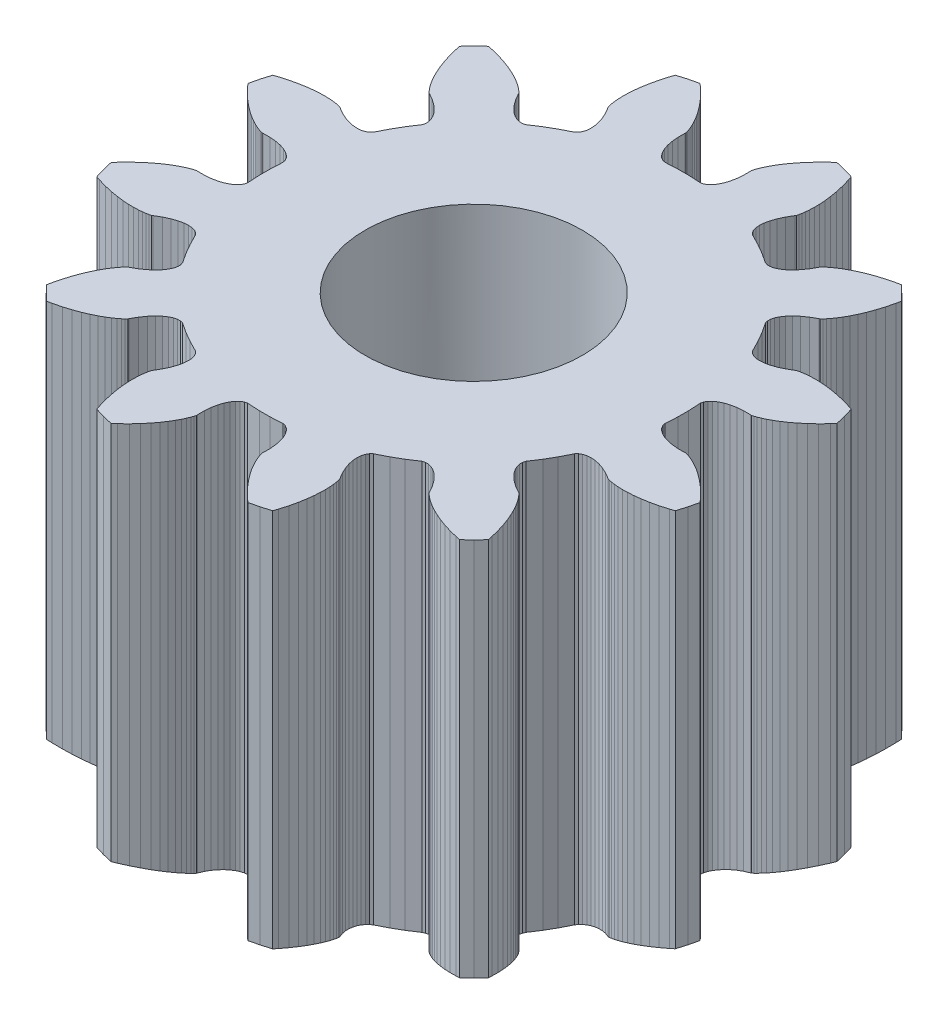
SolidWorks part; units mm, degrees
ref_plane "Front Plane" through (0, 0, 0) normal (0, 0, 1) x (1, 0, 0)
ref_plane "Top Plane" through (0, 0, 0) normal (0, 1, 0) x (1, 0, 0)
ref_plane "Right Plane" through (0, 0, 0) normal (1, 0, 0) x (0, 0, -1)
sketch "Sketch4" plane through (0, 0, 0) normal (0, 1, 0) x (1, 0, 0)
  line L0 (-8.5142, 2.5915) -> (-8.6005, 2.3068)
  line L1 (-8.6005, 2.3068) -> (-8.6681, 2.017)
  line L2 (-8.6681, 2.017) -> (-8.5825, 1.919)
  line L3 (-8.5825, 1.919) -> (-8.4064, 1.7373)
  line L4 (-8.4064, 1.7373) -> (-8.2355, 1.5786)
  line L5 (-8.2355, 1.5786) -> (-8.0717, 1.4418)
  line L6 (-8.0717, 1.4418) -> (-7.9169, 1.3256)
  line L7 (-7.9169, 1.3256) -> (-7.7726, 1.2287)
  line L8 (-7.7726, 1.2287) -> (-7.6405, 1.1497)
  line L9 (-7.6405, 1.1497) -> (-7.522, 1.087)
  line L10 (-7.522, 1.087) -> (-7.4183, 1.0389)
  line L11 (-7.4183, 1.0389) -> (-7.3306, 1.0037)
  line L12 (-7.3306, 1.0037) -> (-7.26, 0.9795)
  line L13 (-7.26, 0.9795) -> (-7.2073, 0.9645)
  line L14 (-7.2073, 0.9645) -> (-7.201, 0.9631)
  line L15 (-7.201, 0.9631) -> (-7.1713, 0.9658)
  line L16 (-7.1713, 0.9658) -> (-6.9676, 0.9668)
  line L17 (-6.9676, 0.9668) -> (-6.7838, 0.9501)
  line L18 (-6.7838, 0.9501) -> (-6.6212, 0.9179)
  line L19 (-6.6212, 0.9179) -> (-6.4809, 0.8724)
  line L20 (-6.4809, 0.8724) -> (-6.3638, 0.8157)
  line L21 (-6.3638, 0.8157) -> (-6.2706, 0.7503)
  line L22 (-6.2706, 0.7503) -> (-6.2018, 0.6785)
  line L23 (-6.2018, 0.6785) -> (-6.1577, 0.6025)
  line L24 (-6.1577, 0.6025) -> (-6.1387, 0.525)
  line L25 (-6.1387, 0.525) -> (-6.1577, 0.1615)
  line L26 (-6.1577, 0.1615) -> (-6.1577, -0.1615)
  line L27 (-6.1577, -0.1615) -> (-6.1387, -0.525)
  line L28 (-6.1387, -0.525) -> (-6.1577, -0.6025)
  line L29 (-6.1577, -0.6025) -> (-6.2018, -0.6785)
  line L30 (-6.2018, -0.6785) -> (-6.2706, -0.7503)
  line L31 (-6.2706, -0.7503) -> (-6.3638, -0.8157)
  line L32 (-6.3638, -0.8157) -> (-6.4809, -0.8724)
  line L33 (-6.4809, -0.8724) -> (-6.6212, -0.9179)
  line L34 (-6.6212, -0.9179) -> (-6.7838, -0.9501)
  line L35 (-6.7838, -0.9501) -> (-6.9676, -0.9668)
  line L36 (-6.9676, -0.9668) -> (-7.1713, -0.9658)
  line L37 (-7.1713, -0.9658) -> (-7.201, -0.9631)
  line L38 (-7.201, -0.9631) -> (-7.2073, -0.9645)
  line L39 (-7.2073, -0.9645) -> (-7.26, -0.9795)
  line L40 (-7.26, -0.9795) -> (-7.3306, -1.0037)
  line L41 (-7.3306, -1.0037) -> (-7.4183, -1.0389)
  line L42 (-7.4183, -1.0389) -> (-7.522, -1.087)
  line L43 (-7.522, -1.087) -> (-7.6405, -1.1497)
  line L44 (-7.6405, -1.1497) -> (-7.7726, -1.2287)
  line L45 (-7.7726, -1.2287) -> (-7.9169, -1.3256)
  line L46 (-7.9169, -1.3256) -> (-8.0717, -1.4418)
  line L47 (-8.0717, -1.4418) -> (-8.2355, -1.5786)
  line L48 (-8.2355, -1.5786) -> (-8.4064, -1.7373)
  line L49 (-8.4064, -1.7373) -> (-8.5825, -1.919)
  line L50 (-8.5825, -1.919) -> (-8.6681, -2.017)
  line L51 (-8.6681, -2.017) -> (-8.6005, -2.3068)
  line L52 (-8.6005, -2.3068) -> (-8.5142, -2.5915)
  line L53 (-8.5142, -2.5915) -> (-8.391, -2.6336)
  line L54 (-8.391, -2.6336) -> (-8.1477, -2.7029)
  line L55 (-8.1477, -2.7029) -> (-7.9203, -2.7549)
  line L56 (-7.9203, -2.7549) -> (-7.7101, -2.7915)
  line L57 (-7.7101, -2.7915) -> (-7.5179, -2.8147)
  line L58 (-7.5179, -2.8147) -> (-7.3445, -2.8264)
  line L59 (-7.3445, -2.8264) -> (-7.1906, -2.8288)
  line L60 (-7.1906, -2.8288) -> (-7.0566, -2.8239)
  line L61 (-7.0566, -2.8239) -> (-6.9428, -2.8137)
  line L62 (-6.9428, -2.8137) -> (-6.8492, -2.8003)
  line L63 (-6.8492, -2.8003) -> (-6.776, -2.7859)
  line L64 (-6.776, -2.7859) -> (-6.7228, -2.7726)
  line L65 (-6.7228, -2.7726) -> (-6.7167, -2.7707)
  line L66 (-6.7167, -2.7707) -> (-6.6923, -2.7535)
  line L67 (-6.6923, -2.7535) -> (-6.5163, -2.6507)
  line L68 (-6.5163, -2.6507) -> (-6.3489, -2.5733)
  line L69 (-6.3489, -2.5733) -> (-6.192, -2.5199)
  line L70 (-6.192, -2.5199) -> (-6.0477, -2.4892)
  line L71 (-6.0477, -2.4892) -> (-5.918, -2.4797)
  line L72 (-5.918, -2.4797) -> (-5.8045, -2.4897)
  line L73 (-5.8045, -2.4897) -> (-5.709, -2.5176)
  line L74 (-5.709, -2.5176) -> (-5.6329, -2.5613)
  line L75 (-5.6329, -2.5613) -> (-5.5776, -2.6189)
  line L76 (-5.5776, -2.6189) -> (-5.4124, -2.9433)
  line L77 (-5.4124, -2.9433) -> (-5.2509, -3.2229)
  line L78 (-5.2509, -3.2229) -> (-5.0526, -3.5282)
  line L79 (-5.0526, -3.5282) -> (-5.0304, -3.6049)
  line L80 (-5.0304, -3.6049) -> (-5.0305, -3.6927)
  line L81 (-5.0305, -3.6927) -> (-5.0542, -3.7893)
  line L82 (-5.0542, -3.7893) -> (-5.1022, -3.8926)
  line L83 (-5.1022, -3.8926) -> (-5.1753, -4.0002)
  line L84 (-5.1753, -4.0002) -> (-5.2741, -4.1098)
  line L85 (-5.2741, -4.1098) -> (-5.3987, -4.219)
  line L86 (-5.3987, -4.219) -> (-5.5496, -4.3253)
  line L87 (-5.5496, -4.3253) -> (-5.7265, -4.4263)
  line L88 (-5.7265, -4.4263) -> (-5.7536, -4.4388)
  line L89 (-5.7536, -4.4388) -> (-5.7583, -4.4432)
  line L90 (-5.7583, -4.4432) -> (-5.7965, -4.4825)
  line L91 (-5.7965, -4.4825) -> (-5.8455, -4.5388)
  line L92 (-5.8455, -4.5388) -> (-5.9039, -4.6131)
  line L93 (-5.9039, -4.6131) -> (-5.9696, -4.7066)
  line L94 (-5.9696, -4.7066) -> (-6.0409, -4.8202)
  line L95 (-6.0409, -4.8202) -> (-6.1158, -4.9546)
  line L96 (-6.1158, -4.9546) -> (-6.1923, -5.1107)
  line L97 (-6.1923, -5.1107) -> (-6.2683, -5.2887)
  line L98 (-6.2683, -5.2887) -> (-6.3417, -5.4891)
  line L99 (-6.3417, -5.4891) -> (-6.4104, -5.712)
  line L100 (-6.4104, -5.712) -> (-6.4721, -5.9574)
  line L101 (-6.4721, -5.9574) -> (-6.4972, -6.085)
  line L102 (-6.4972, -6.085) -> (-6.2938, -6.3022)
  line L103 (-6.2938, -6.3022) -> (-6.0766, -6.5056)
  line L104 (-6.0766, -6.5056) -> (-5.9489, -6.4805)
  line L105 (-5.9489, -6.4805) -> (-5.7035, -6.4188)
  line L106 (-5.7035, -6.4188) -> (-5.4806, -6.3502)
  line L107 (-5.4806, -6.3502) -> (-5.2802, -6.2768)
  line L108 (-5.2802, -6.2768) -> (-5.1022, -6.2008)
  line L109 (-5.1022, -6.2008) -> (-4.9462, -6.1243)
  line L110 (-4.9462, -6.1243) -> (-4.8117, -6.0494)
  line L111 (-4.8117, -6.0494) -> (-4.6981, -5.9781)
  line L112 (-4.6981, -5.9781) -> (-4.6046, -5.9123)
  line L113 (-4.6046, -5.9123) -> (-4.5303, -5.854)
  line L114 (-4.5303, -5.854) -> (-4.4741, -5.8049)
  line L115 (-4.4741, -5.8049) -> (-4.4347, -5.7667)
  line L116 (-4.4347, -5.7667) -> (-4.4304, -5.7621)
  line L117 (-4.4304, -5.7621) -> (-4.4178, -5.7349)
  line L118 (-4.4178, -5.7349) -> (-4.3168, -5.558)
  line L119 (-4.3168, -5.558) -> (-4.2105, -5.4072)
  line L120 (-4.2105, -5.4072) -> (-4.1013, -5.2825)
  line L121 (-4.1013, -5.2825) -> (-3.9917, -5.1838)
  line L122 (-3.9917, -5.1838) -> (-3.8841, -5.1107)
  line L123 (-3.8841, -5.1107) -> (-3.7809, -5.0626)
  line L124 (-3.7809, -5.0626) -> (-3.6842, -5.039)
  line L125 (-3.6842, -5.039) -> (-3.5965, -5.0388)
  line L126 (-3.5965, -5.0388) -> (-3.5198, -5.0611)
  line L127 (-3.5198, -5.0611) -> (-3.2145, -5.2594)
  line L128 (-3.2145, -5.2594) -> (-2.9348, -5.4208)
  line L129 (-2.9348, -5.4208) -> (-2.6105, -5.5861)
  line L130 (-2.6105, -5.5861) -> (-2.5528, -5.6414)
  line L131 (-2.5528, -5.6414) -> (-2.5091, -5.7174)
  line L132 (-2.5091, -5.7174) -> (-2.4813, -5.813)
  line L133 (-2.4813, -5.813) -> (-2.4712, -5.9264)
  line L134 (-2.4712, -5.9264) -> (-2.4807, -6.0562)
  line L135 (-2.4807, -6.0562) -> (-2.5114, -6.2004)
  line L136 (-2.5114, -6.2004) -> (-2.5648, -6.3573)
  line L137 (-2.5648, -6.3573) -> (-2.6423, -6.5248)
  line L138 (-2.6423, -6.5248) -> (-2.745, -6.7007)
  line L139 (-2.745, -6.7007) -> (-2.7622, -6.7252)
  line L140 (-2.7622, -6.7252) -> (-2.7641, -6.7313)
  line L141 (-2.7641, -6.7313) -> (-2.7775, -6.7844)
  line L142 (-2.7775, -6.7844) -> (-2.7919, -6.8577)
  line L143 (-2.7919, -6.8577) -> (-2.8052, -6.9512)
  line L144 (-2.8052, -6.9512) -> (-2.8154, -7.065)
  line L145 (-2.8154, -7.065) -> (-2.8204, -7.1991)
  line L146 (-2.8204, -7.1991) -> (-2.818, -7.353)
  line L147 (-2.818, -7.353) -> (-2.8062, -7.5263)
  line L148 (-2.8062, -7.5263) -> (-2.783, -7.7185)
  line L149 (-2.783, -7.7185) -> (-2.7464, -7.9288)
  line L150 (-2.7464, -7.9288) -> (-2.6944, -8.1561)
  line L151 (-2.6944, -8.1561) -> (-2.6252, -8.3995)
  line L152 (-2.6252, -8.3995) -> (-2.5831, -8.5226)
  line L153 (-2.5831, -8.5226) -> (-2.2983, -8.609)
  line L154 (-2.2983, -8.609) -> (-2.0085, -8.6766)
  line L155 (-2.0085, -8.6766) -> (-1.9105, -8.591)
  line L156 (-1.9105, -8.591) -> (-1.7288, -8.4148)
  line L157 (-1.7288, -8.4148) -> (-1.5701, -8.2439)
  line L158 (-1.5701, -8.2439) -> (-1.4333, -8.0802)
  line L159 (-1.4333, -8.0802) -> (-1.3171, -7.9253)
  line L160 (-1.3171, -7.9253) -> (-1.2203, -7.7811)
  line L161 (-1.2203, -7.7811) -> (-1.1413, -7.649)
  line L162 (-1.1413, -7.649) -> (-1.0785, -7.5304)
  line L163 (-1.0785, -7.5304) -> (-1.0304, -7.4268)
  line L164 (-1.0304, -7.4268) -> (-0.9952, -7.3391)
  line L165 (-0.9952, -7.3391) -> (-0.9711, -7.2685)
  line L166 (-0.9711, -7.2685) -> (-0.9561, -7.2157)
  line L167 (-0.9561, -7.2157) -> (-0.9547, -7.2095)
  line L168 (-0.9547, -7.2095) -> (-0.9573, -7.1797)
  line L169 (-0.9573, -7.1797) -> (-0.9583, -6.976)
  line L170 (-0.9583, -6.976) -> (-0.9417, -6.7922)
  line L171 (-0.9417, -6.7922) -> (-0.9095, -6.6297)
  line L172 (-0.9095, -6.6297) -> (-0.8639, -6.4894)
  line L173 (-0.8639, -6.4894) -> (-0.8073, -6.3723)
  line L174 (-0.8073, -6.3723) -> (-0.7419, -6.279)
  line L175 (-0.7419, -6.279) -> (-0.67, -6.2102)
  line L176 (-0.67, -6.2102) -> (-0.5941, -6.1662)
  line L177 (-0.5941, -6.1662) -> (-0.5165, -6.1471)
  line L178 (-0.5165, -6.1471) -> (-0.153, -6.1662)
  line L179 (-0.153, -6.1662) -> (0.1699, -6.1662)
  line L180 (0.1699, -6.1662) -> (0.5334, -6.1471)
  line L181 (0.5334, -6.1471) -> (0.611, -6.1662)
  line L182 (0.611, -6.1662) -> (0.6869, -6.2102)
  line L183 (0.6869, -6.2102) -> (0.7588, -6.279)
  line L184 (0.7588, -6.279) -> (0.8242, -6.3723)
  line L185 (0.8242, -6.3723) -> (0.8808, -6.4894)
  line L186 (0.8808, -6.4894) -> (0.9264, -6.6297)
  line L187 (0.9264, -6.6297) -> (0.9586, -6.7922)
  line L188 (0.9586, -6.7922) -> (0.9752, -6.976)
  line L189 (0.9752, -6.976) -> (0.9742, -7.1797)
  line L190 (0.9742, -7.1797) -> (0.9716, -7.2095)
  line L191 (0.9716, -7.2095) -> (0.973, -7.2157)
  line L192 (0.973, -7.2157) -> (0.988, -7.2685)
  line L193 (0.988, -7.2685) -> (1.0121, -7.3391)
  line L194 (1.0121, -7.3391) -> (1.0474, -7.4268)
  line L195 (1.0474, -7.4268) -> (1.0954, -7.5304)
  line L196 (1.0954, -7.5304) -> (1.1582, -7.649)
  line L197 (1.1582, -7.649) -> (1.2372, -7.7811)
  line L198 (1.2372, -7.7811) -> (1.334, -7.9253)
  line L199 (1.334, -7.9253) -> (1.4502, -8.0802)
  line L200 (1.4502, -8.0802) -> (1.587, -8.2439)
  line L201 (1.587, -8.2439) -> (1.7457, -8.4148)
  line L202 (1.7457, -8.4148) -> (1.9274, -8.591)
  line L203 (1.9274, -8.591) -> (2.0254, -8.6766)
  line L204 (2.0254, -8.6766) -> (2.3152, -8.609)
  line L205 (2.3152, -8.609) -> (2.6, -8.5226)
  line L206 (2.6, -8.5226) -> (2.6421, -8.3995)
  line L207 (2.6421, -8.3995) -> (2.7113, -8.1561)
  line L208 (2.7113, -8.1561) -> (2.7633, -7.9288)
  line L209 (2.7633, -7.9288) -> (2.7999, -7.7185)
  line L210 (2.7999, -7.7185) -> (2.8231, -7.5263)
  line L211 (2.8231, -7.5263) -> (2.8349, -7.353)
  line L212 (2.8349, -7.353) -> (2.8373, -7.1991)
  line L213 (2.8373, -7.1991) -> (2.8323, -7.065)
  line L214 (2.8323, -7.065) -> (2.8221, -6.9512)
  line L215 (2.8221, -6.9512) -> (2.8088, -6.8577)
  line L216 (2.8088, -6.8577) -> (2.7944, -6.7844)
  line L217 (2.7944, -6.7844) -> (2.781, -6.7313)
  line L218 (2.781, -6.7313) -> (2.7791, -6.7252)
  line L219 (2.7791, -6.7252) -> (2.7619, -6.7007)
  line L220 (2.7619, -6.7007) -> (2.6592, -6.5248)
  line L221 (2.6592, -6.5248) -> (2.5817, -6.3573)
  line L222 (2.5817, -6.3573) -> (2.5283, -6.2004)
  line L223 (2.5283, -6.2004) -> (2.4976, -6.0562)
  line L224 (2.4976, -6.0562) -> (2.4881, -5.9264)
  line L225 (2.4881, -5.9264) -> (2.4982, -5.813)
  line L226 (2.4982, -5.813) -> (2.526, -5.7174)
  line L227 (2.526, -5.7174) -> (2.5697, -5.6414)
  line L228 (2.5697, -5.6414) -> (2.6274, -5.5861)
  line L229 (2.6274, -5.5861) -> (2.9517, -5.4208)
  line L230 (2.9517, -5.4208) -> (3.2314, -5.2594)
  line L231 (3.2314, -5.2594) -> (3.5367, -5.0611)
  line L232 (3.5367, -5.0611) -> (3.6134, -5.0388)
  line L233 (3.6134, -5.0388) -> (3.7011, -5.039)
  line L234 (3.7011, -5.039) -> (3.7978, -5.0626)
  line L235 (3.7978, -5.0626) -> (3.901, -5.1107)
  line L236 (3.901, -5.1107) -> (4.0087, -5.1838)
  line L237 (4.0087, -5.1838) -> (4.1182, -5.2825)
  line L238 (4.1182, -5.2825) -> (4.2274, -5.4072)
  line L239 (4.2274, -5.4072) -> (4.3337, -5.558)
  line L240 (4.3337, -5.558) -> (4.4347, -5.7349)
  line L241 (4.4347, -5.7349) -> (4.4473, -5.7621)
  line L242 (4.4473, -5.7621) -> (4.4516, -5.7667)
  line L243 (4.4516, -5.7667) -> (4.491, -5.8049)
  line L244 (4.491, -5.8049) -> (4.5472, -5.854)
  line L245 (4.5472, -5.854) -> (4.6215, -5.9123)
  line L246 (4.6215, -5.9123) -> (4.715, -5.9781)
  line L247 (4.715, -5.9781) -> (4.8286, -6.0494)
  line L248 (4.8286, -6.0494) -> (4.9631, -6.1243)
  line L249 (4.9631, -6.1243) -> (5.1191, -6.2008)
  line L250 (5.1191, -6.2008) -> (5.2971, -6.2768)
  line L251 (5.2971, -6.2768) -> (5.4975, -6.3502)
  line L252 (5.4975, -6.3502) -> (5.7204, -6.4188)
  line L253 (5.7204, -6.4188) -> (5.9658, -6.4805)
  line L254 (5.9658, -6.4805) -> (6.0935, -6.5056)
  line L255 (6.0935, -6.5056) -> (6.3107, -6.3022)
  line L256 (6.3107, -6.3022) -> (6.5141, -6.085)
  line L257 (6.5141, -6.085) -> (6.489, -5.9574)
  line L258 (6.489, -5.9574) -> (6.4273, -5.712)
  line L259 (6.4273, -5.712) -> (6.3586, -5.4891)
  line L260 (6.3586, -5.4891) -> (6.2852, -5.2887)
  line L261 (6.2852, -5.2887) -> (6.2092, -5.1107)
  line L262 (6.2092, -5.1107) -> (6.1327, -4.9546)
  line L263 (6.1327, -4.9546) -> (6.0578, -4.8202)
  line L264 (6.0578, -4.8202) -> (5.9865, -4.7066)
  line L265 (5.9865, -4.7066) -> (5.9208, -4.6131)
  line L266 (5.9208, -4.6131) -> (5.8624, -4.5388)
  line L267 (5.8624, -4.5388) -> (5.8134, -4.4825)
  line L268 (5.8134, -4.4825) -> (5.7752, -4.4432)
  line L269 (5.7752, -4.4432) -> (5.7705, -4.4388)
  line L270 (5.7705, -4.4388) -> (5.7434, -4.4263)
  line L271 (5.7434, -4.4263) -> (5.5665, -4.3253)
  line L272 (5.5665, -4.3253) -> (5.4156, -4.219)
  line L273 (5.4156, -4.219) -> (5.291, -4.1098)
  line L274 (5.291, -4.1098) -> (5.1922, -4.0002)
  line L275 (5.1922, -4.0002) -> (5.1191, -3.8926)
  line L276 (5.1191, -3.8926) -> (5.0711, -3.7893)
  line L277 (5.0711, -3.7893) -> (5.0474, -3.6927)
  line L278 (5.0474, -3.6927) -> (5.0473, -3.6049)
  line L279 (5.0473, -3.6049) -> (5.0695, -3.5282)
  line L280 (5.0695, -3.5282) -> (5.2678, -3.2229)
  line L281 (5.2678, -3.2229) -> (5.4293, -2.9433)
  line L282 (5.4293, -2.9433) -> (5.5945, -2.6189)
  line L283 (5.5945, -2.6189) -> (5.6498, -2.5613)
  line L284 (5.6498, -2.5613) -> (5.7259, -2.5176)
  line L285 (5.7259, -2.5176) -> (5.8214, -2.4897)
  line L286 (5.8214, -2.4897) -> (5.9349, -2.4797)
  line L287 (5.9349, -2.4797) -> (6.0646, -2.4892)
  line L288 (6.0646, -2.4892) -> (6.2089, -2.5199)
  line L289 (6.2089, -2.5199) -> (6.3658, -2.5733)
  line L290 (6.3658, -2.5733) -> (6.5332, -2.6507)
  line L291 (6.5332, -2.6507) -> (6.7092, -2.7535)
  line L292 (6.7092, -2.7535) -> (6.7336, -2.7707)
  line L293 (6.7336, -2.7707) -> (6.7397, -2.7726)
  line L294 (6.7397, -2.7726) -> (6.7929, -2.7859)
  line L295 (6.7929, -2.7859) -> (6.8661, -2.8003)
  line L296 (6.8661, -2.8003) -> (6.9597, -2.8137)
  line L297 (6.9597, -2.8137) -> (7.0735, -2.8239)
  line L298 (7.0735, -2.8239) -> (7.2075, -2.8288)
  line L299 (7.2075, -2.8288) -> (7.3614, -2.8264)
  line L300 (7.3614, -2.8264) -> (7.5348, -2.8147)
  line L301 (7.5348, -2.8147) -> (7.727, -2.7915)
  line L302 (7.727, -2.7915) -> (7.9372, -2.7549)
  line L303 (7.9372, -2.7549) -> (8.1646, -2.7029)
  line L304 (8.1646, -2.7029) -> (8.4079, -2.6336)
  line L305 (8.4079, -2.6336) -> (8.5311, -2.5915)
  line L306 (8.5311, -2.5915) -> (8.6174, -2.3068)
  line L307 (8.6174, -2.3068) -> (8.685, -2.017)
  line L308 (8.685, -2.017) -> (8.5994, -1.919)
  line L309 (8.5994, -1.919) -> (8.4233, -1.7373)
  line L310 (8.4233, -1.7373) -> (8.2524, -1.5786)
  line L311 (8.2524, -1.5786) -> (8.0886, -1.4418)
  line L312 (8.0886, -1.4418) -> (7.9338, -1.3256)
  line L313 (7.9338, -1.3256) -> (7.7895, -1.2287)
  line L314 (7.7895, -1.2287) -> (7.6574, -1.1497)
  line L315 (7.6574, -1.1497) -> (7.5389, -1.087)
  line L316 (7.5389, -1.087) -> (7.4352, -1.0389)
  line L317 (7.4352, -1.0389) -> (7.3475, -1.0037)
  line L318 (7.3475, -1.0037) -> (7.2769, -0.9795)
  line L319 (7.2769, -0.9795) -> (7.2242, -0.9645)
  line L320 (7.2242, -0.9645) -> (7.218, -0.9631)
  line L321 (7.218, -0.9631) -> (7.1882, -0.9658)
  line L322 (7.1882, -0.9658) -> (6.9845, -0.9668)
  line L323 (6.9845, -0.9668) -> (6.8007, -0.9501)
  line L324 (6.8007, -0.9501) -> (6.6381, -0.9179)
  line L325 (6.6381, -0.9179) -> (6.4978, -0.8724)
  line L326 (6.4978, -0.8724) -> (6.3807, -0.8157)
  line L327 (6.3807, -0.8157) -> (6.2875, -0.7503)
  line L328 (6.2875, -0.7503) -> (6.2187, -0.6785)
  line L329 (6.2187, -0.6785) -> (6.1747, -0.6025)
  line L330 (6.1747, -0.6025) -> (6.1556, -0.525)
  line L331 (6.1556, -0.525) -> (6.1747, -0.1615)
  line L332 (6.1747, -0.1615) -> (6.1747, 0.1615)
  line L333 (6.1747, 0.1615) -> (6.1556, 0.525)
  line L334 (6.1556, 0.525) -> (6.1747, 0.6025)
  line L335 (6.1747, 0.6025) -> (6.2187, 0.6785)
  line L336 (6.2187, 0.6785) -> (6.2875, 0.7503)
  line L337 (6.2875, 0.7503) -> (6.3807, 0.8157)
  line L338 (6.3807, 0.8157) -> (6.4978, 0.8724)
  line L339 (6.4978, 0.8724) -> (6.6381, 0.9179)
  line L340 (6.6381, 0.9179) -> (6.8007, 0.9501)
  line L341 (6.8007, 0.9501) -> (6.9845, 0.9668)
  line L342 (6.9845, 0.9668) -> (7.1882, 0.9658)
  line L343 (7.1882, 0.9658) -> (7.218, 0.9631)
  line L344 (7.218, 0.9631) -> (7.2242, 0.9645)
  line L345 (7.2242, 0.9645) -> (7.2769, 0.9795)
  line L346 (7.2769, 0.9795) -> (7.3475, 1.0037)
  line L347 (7.3475, 1.0037) -> (7.4352, 1.0389)
  line L348 (7.4352, 1.0389) -> (7.5389, 1.087)
  line L349 (7.5389, 1.087) -> (7.6574, 1.1497)
  line L350 (7.6574, 1.1497) -> (7.7895, 1.2287)
  line L351 (7.7895, 1.2287) -> (7.9338, 1.3256)
  line L352 (7.9338, 1.3256) -> (8.0886, 1.4418)
  line L353 (8.0886, 1.4418) -> (8.2524, 1.5786)
  line L354 (8.2524, 1.5786) -> (8.4233, 1.7373)
  line L355 (8.4233, 1.7373) -> (8.5994, 1.919)
  line L356 (8.5994, 1.919) -> (8.685, 2.017)
  line L357 (8.685, 2.017) -> (8.6174, 2.3068)
  line L358 (8.6174, 2.3068) -> (8.5311, 2.5915)
  line L359 (8.5311, 2.5915) -> (8.4079, 2.6336)
  line L360 (8.4079, 2.6336) -> (8.1646, 2.7029)
  line L361 (8.1646, 2.7029) -> (7.9372, 2.7549)
  line L362 (7.9372, 2.7549) -> (7.727, 2.7915)
  line L363 (7.727, 2.7915) -> (7.5348, 2.8147)
  line L364 (7.5348, 2.8147) -> (7.3614, 2.8264)
  line L365 (7.3614, 2.8264) -> (7.2075, 2.8288)
  line L366 (7.2075, 2.8288) -> (7.0735, 2.8239)
  line L367 (7.0735, 2.8239) -> (6.9597, 2.8137)
  line L368 (6.9597, 2.8137) -> (6.8661, 2.8003)
  line L369 (6.8661, 2.8003) -> (6.7929, 2.7859)
  line L370 (6.7929, 2.7859) -> (6.7397, 2.7726)
  line L371 (6.7397, 2.7726) -> (6.7336, 2.7707)
  line L372 (6.7336, 2.7707) -> (6.7092, 2.7535)
  line L373 (6.7092, 2.7535) -> (6.5332, 2.6507)
  line L374 (6.5332, 2.6507) -> (6.3658, 2.5733)
  line L375 (6.3658, 2.5733) -> (6.2089, 2.5199)
  line L376 (6.2089, 2.5199) -> (6.0646, 2.4892)
  line L377 (6.0646, 2.4892) -> (5.9349, 2.4797)
  line L378 (5.9349, 2.4797) -> (5.8214, 2.4897)
  line L379 (5.8214, 2.4897) -> (5.7259, 2.5176)
  line L380 (5.7259, 2.5176) -> (5.6498, 2.5613)
  line L381 (5.6498, 2.5613) -> (5.5945, 2.6189)
  line L382 (5.5945, 2.6189) -> (5.4293, 2.9433)
  line L383 (5.4293, 2.9433) -> (5.2678, 3.2229)
  line L384 (5.2678, 3.2229) -> (5.0695, 3.5282)
  line L385 (5.0695, 3.5282) -> (5.0473, 3.6049)
  line L386 (5.0473, 3.6049) -> (5.0474, 3.6927)
  line L387 (5.0474, 3.6927) -> (5.0711, 3.7893)
  line L388 (5.0711, 3.7893) -> (5.1191, 3.8926)
  line L389 (5.1191, 3.8926) -> (5.1922, 4.0002)
  line L390 (5.1922, 4.0002) -> (5.291, 4.1098)
  line L391 (5.291, 4.1098) -> (5.4156, 4.219)
  line L392 (5.4156, 4.219) -> (5.5665, 4.3253)
  line L393 (5.5665, 4.3253) -> (5.7434, 4.4263)
  line L394 (5.7434, 4.4263) -> (5.7705, 4.4388)
  line L395 (5.7705, 4.4388) -> (5.7752, 4.4432)
  line L396 (5.7752, 4.4432) -> (5.8134, 4.4825)
  line L397 (5.8134, 4.4825) -> (5.8624, 4.5388)
  line L398 (5.8624, 4.5388) -> (5.9208, 4.6131)
  line L399 (5.9208, 4.6131) -> (5.9865, 4.7066)
  line L400 (5.9865, 4.7066) -> (6.0578, 4.8202)
  line L401 (6.0578, 4.8202) -> (6.1327, 4.9546)
  line L402 (6.1327, 4.9546) -> (6.2092, 5.1107)
  line L403 (6.2092, 5.1107) -> (6.2852, 5.2887)
  line L404 (6.2852, 5.2887) -> (6.3586, 5.4891)
  line L405 (6.3586, 5.4891) -> (6.4273, 5.712)
  line L406 (6.4273, 5.712) -> (6.489, 5.9574)
  line L407 (6.489, 5.9574) -> (6.5141, 6.085)
  line L408 (6.5141, 6.085) -> (6.3107, 6.3022)
  line L409 (6.3107, 6.3022) -> (6.0935, 6.5056)
  line L410 (6.0935, 6.5056) -> (5.9658, 6.4805)
  line L411 (5.9658, 6.4805) -> (5.7204, 6.4188)
  line L412 (5.7204, 6.4188) -> (5.4975, 6.3502)
  line L413 (5.4975, 6.3502) -> (5.2971, 6.2768)
  line L414 (5.2971, 6.2768) -> (5.1191, 6.2008)
  line L415 (5.1191, 6.2008) -> (4.9631, 6.1243)
  line L416 (4.9631, 6.1243) -> (4.8286, 6.0494)
  line L417 (4.8286, 6.0494) -> (4.715, 5.9781)
  line L418 (4.715, 5.9781) -> (4.6215, 5.9123)
  line L419 (4.6215, 5.9123) -> (4.5472, 5.854)
  line L420 (4.5472, 5.854) -> (4.491, 5.8049)
  line L421 (4.491, 5.8049) -> (4.4516, 5.7667)
  line L422 (4.4516, 5.7667) -> (4.4473, 5.7621)
  line L423 (4.4473, 5.7621) -> (4.4347, 5.7349)
  line L424 (4.4347, 5.7349) -> (4.3337, 5.558)
  line L425 (4.3337, 5.558) -> (4.2274, 5.4072)
  line L426 (4.2274, 5.4072) -> (4.1182, 5.2825)
  line L427 (4.1182, 5.2825) -> (4.0087, 5.1838)
  line L428 (4.0087, 5.1838) -> (3.901, 5.1107)
  line L429 (3.901, 5.1107) -> (3.7978, 5.0626)
  line L430 (3.7978, 5.0626) -> (3.7011, 5.039)
  line L431 (3.7011, 5.039) -> (3.6134, 5.0388)
  line L432 (3.6134, 5.0388) -> (3.5367, 5.0611)
  line L433 (3.5367, 5.0611) -> (3.2314, 5.2594)
  line L434 (3.2314, 5.2594) -> (2.9517, 5.4208)
  line L435 (2.9517, 5.4208) -> (2.6274, 5.5861)
  line L436 (2.6274, 5.5861) -> (2.5697, 5.6414)
  line L437 (2.5697, 5.6414) -> (2.526, 5.7174)
  line L438 (2.526, 5.7174) -> (2.4982, 5.813)
  line L439 (2.4982, 5.813) -> (2.4881, 5.9264)
  line L440 (2.4881, 5.9264) -> (2.4976, 6.0562)
  line L441 (2.4976, 6.0562) -> (2.5283, 6.2004)
  line L442 (2.5283, 6.2004) -> (2.5817, 6.3573)
  line L443 (2.5817, 6.3573) -> (2.6592, 6.5248)
  line L444 (2.6592, 6.5248) -> (2.7619, 6.7007)
  line L445 (2.7619, 6.7007) -> (2.7791, 6.7252)
  line L446 (2.7791, 6.7252) -> (2.781, 6.7313)
  line L447 (2.781, 6.7313) -> (2.7944, 6.7844)
  line L448 (2.7944, 6.7844) -> (2.8088, 6.8577)
  line L449 (2.8088, 6.8577) -> (2.8221, 6.9512)
  line L450 (2.8221, 6.9512) -> (2.8323, 7.065)
  line L451 (2.8323, 7.065) -> (2.8373, 7.1991)
  line L452 (2.8373, 7.1991) -> (2.8349, 7.353)
  line L453 (2.8349, 7.353) -> (2.8231, 7.5263)
  line L454 (2.8231, 7.5263) -> (2.7999, 7.7185)
  line L455 (2.7999, 7.7185) -> (2.7633, 7.9288)
  line L456 (2.7633, 7.9288) -> (2.7113, 8.1561)
  line L457 (2.7113, 8.1561) -> (2.6421, 8.3995)
  line L458 (2.6421, 8.3995) -> (2.6, 8.5226)
  line L459 (2.6, 8.5226) -> (2.3152, 8.609)
  line L460 (2.3152, 8.609) -> (2.0254, 8.6766)
  line L461 (2.0254, 8.6766) -> (1.9274, 8.591)
  line L462 (1.9274, 8.591) -> (1.7457, 8.4148)
  line L463 (1.7457, 8.4148) -> (1.587, 8.2439)
  line L464 (1.587, 8.2439) -> (1.4502, 8.0802)
  line L465 (1.4502, 8.0802) -> (1.334, 7.9253)
  line L466 (1.334, 7.9253) -> (1.2372, 7.7811)
  line L467 (1.2372, 7.7811) -> (1.1582, 7.649)
  line L468 (1.1582, 7.649) -> (1.0954, 7.5304)
  line L469 (1.0954, 7.5304) -> (1.0474, 7.4268)
  line L470 (1.0474, 7.4268) -> (1.0121, 7.3391)
  line L471 (1.0121, 7.3391) -> (0.988, 7.2685)
  line L472 (0.988, 7.2685) -> (0.973, 7.2157)
  line L473 (0.973, 7.2157) -> (0.9716, 7.2095)
  line L474 (0.9716, 7.2095) -> (0.9742, 7.1797)
  line L475 (0.9742, 7.1797) -> (0.9752, 6.976)
  line L476 (0.9752, 6.976) -> (0.9586, 6.7922)
  line L477 (0.9586, 6.7922) -> (0.9264, 6.6297)
  line L478 (0.9264, 6.6297) -> (0.8808, 6.4894)
  line L479 (0.8808, 6.4894) -> (0.8242, 6.3723)
  line L480 (0.8242, 6.3723) -> (0.7588, 6.279)
  line L481 (0.7588, 6.279) -> (0.6869, 6.2102)
  line L482 (0.6869, 6.2102) -> (0.611, 6.1662)
  line L483 (0.611, 6.1662) -> (0.5334, 6.1471)
  line L484 (0.5334, 6.1471) -> (0.1699, 6.1662)
  line L485 (0.1699, 6.1662) -> (-0.153, 6.1662)
  line L486 (-0.153, 6.1662) -> (-0.5165, 6.1471)
  line L487 (-0.5165, 6.1471) -> (-0.5941, 6.1662)
  line L488 (-0.5941, 6.1662) -> (-0.67, 6.2102)
  line L489 (-0.67, 6.2102) -> (-0.7419, 6.279)
  line L490 (-0.7419, 6.279) -> (-0.8073, 6.3723)
  line L491 (-0.8073, 6.3723) -> (-0.8639, 6.4894)
  line L492 (-0.8639, 6.4894) -> (-0.9095, 6.6297)
  line L493 (-0.9095, 6.6297) -> (-0.9417, 6.7922)
  line L494 (-0.9417, 6.7922) -> (-0.9583, 6.976)
  line L495 (-0.9583, 6.976) -> (-0.9573, 7.1797)
  line L496 (-0.9573, 7.1797) -> (-0.9547, 7.2095)
  line L497 (-0.9547, 7.2095) -> (-0.9561, 7.2157)
  line L498 (-0.9561, 7.2157) -> (-0.9711, 7.2685)
  line L499 (-0.9711, 7.2685) -> (-0.9952, 7.3391)
  line L500 (-0.9952, 7.3391) -> (-1.0304, 7.4268)
  line L501 (-1.0304, 7.4268) -> (-1.0785, 7.5304)
  line L502 (-1.0785, 7.5304) -> (-1.1413, 7.649)
  line L503 (-1.1413, 7.649) -> (-1.2203, 7.7811)
  line L504 (-1.2203, 7.7811) -> (-1.3171, 7.9253)
  line L505 (-1.3171, 7.9253) -> (-1.4333, 8.0802)
  line L506 (-1.4333, 8.0802) -> (-1.5701, 8.2439)
  line L507 (-1.5701, 8.2439) -> (-1.7288, 8.4148)
  line L508 (-1.7288, 8.4148) -> (-1.9105, 8.591)
  line L509 (-1.9105, 8.591) -> (-2.0085, 8.6766)
  line L510 (-2.0085, 8.6766) -> (-2.2983, 8.609)
  line L511 (-2.2983, 8.609) -> (-2.5831, 8.5226)
  line L512 (-2.5831, 8.5226) -> (-2.6252, 8.3995)
  line L513 (-2.6252, 8.3995) -> (-2.6944, 8.1561)
  line L514 (-2.6944, 8.1561) -> (-2.7464, 7.9288)
  line L515 (-2.7464, 7.9288) -> (-2.783, 7.7185)
  line L516 (-2.783, 7.7185) -> (-2.8062, 7.5263)
  line L517 (-2.8062, 7.5263) -> (-2.818, 7.353)
  line L518 (-2.818, 7.353) -> (-2.8204, 7.1991)
  line L519 (-2.8204, 7.1991) -> (-2.8154, 7.065)
  line L520 (-2.8154, 7.065) -> (-2.8052, 6.9512)
  line L521 (-2.8052, 6.9512) -> (-2.7919, 6.8577)
  line L522 (-2.7919, 6.8577) -> (-2.7775, 6.7844)
  line L523 (-2.7775, 6.7844) -> (-2.7641, 6.7313)
  line L524 (-2.7641, 6.7313) -> (-2.7622, 6.7252)
  line L525 (-2.7622, 6.7252) -> (-2.745, 6.7007)
  line L526 (-2.745, 6.7007) -> (-2.6423, 6.5248)
  line L527 (-2.6423, 6.5248) -> (-2.5648, 6.3573)
  line L528 (-2.5648, 6.3573) -> (-2.5114, 6.2004)
  line L529 (-2.5114, 6.2004) -> (-2.4807, 6.0562)
  line L530 (-2.4807, 6.0562) -> (-2.4712, 5.9264)
  line L531 (-2.4712, 5.9264) -> (-2.4813, 5.813)
  line L532 (-2.4813, 5.813) -> (-2.5091, 5.7174)
  line L533 (-2.5091, 5.7174) -> (-2.5528, 5.6414)
  line L534 (-2.5528, 5.6414) -> (-2.6105, 5.5861)
  line L535 (-2.6105, 5.5861) -> (-2.9348, 5.4208)
  line L536 (-2.9348, 5.4208) -> (-3.2145, 5.2594)
  line L537 (-3.2145, 5.2594) -> (-3.5198, 5.0611)
  line L538 (-3.5198, 5.0611) -> (-3.5965, 5.0388)
  line L539 (-3.5965, 5.0388) -> (-3.6842, 5.039)
  line L540 (-3.6842, 5.039) -> (-3.7809, 5.0626)
  line L541 (-3.7809, 5.0626) -> (-3.8841, 5.1107)
  line L542 (-3.8841, 5.1107) -> (-3.9917, 5.1838)
  line L543 (-3.9917, 5.1838) -> (-4.1013, 5.2825)
  line L544 (-4.1013, 5.2825) -> (-4.2105, 5.4072)
  line L545 (-4.2105, 5.4072) -> (-4.3168, 5.558)
  line L546 (-4.3168, 5.558) -> (-4.4178, 5.7349)
  line L547 (-4.4178, 5.7349) -> (-4.4304, 5.7621)
  line L548 (-4.4304, 5.7621) -> (-4.4347, 5.7667)
  line L549 (-4.4347, 5.7667) -> (-4.4741, 5.8049)
  line L550 (-4.4741, 5.8049) -> (-4.5303, 5.854)
  line L551 (-4.5303, 5.854) -> (-4.6046, 5.9123)
  line L552 (-4.6046, 5.9123) -> (-4.6981, 5.9781)
  line L553 (-4.6981, 5.9781) -> (-4.8117, 6.0494)
  line L554 (-4.8117, 6.0494) -> (-4.9462, 6.1243)
  line L555 (-4.9462, 6.1243) -> (-5.1022, 6.2008)
  line L556 (-5.1022, 6.2008) -> (-5.2802, 6.2768)
  line L557 (-5.2802, 6.2768) -> (-5.4806, 6.3502)
  line L558 (-5.4806, 6.3502) -> (-5.7035, 6.4188)
  line L559 (-5.7035, 6.4188) -> (-5.9489, 6.4805)
  line L560 (-5.9489, 6.4805) -> (-6.0766, 6.5056)
  line L561 (-6.0766, 6.5056) -> (-6.2938, 6.3022)
  line L562 (-6.2938, 6.3022) -> (-6.4972, 6.085)
  line L563 (-6.4972, 6.085) -> (-6.4721, 5.9574)
  line L564 (-6.4721, 5.9574) -> (-6.4104, 5.712)
  line L565 (-6.4104, 5.712) -> (-6.3417, 5.4891)
  line L566 (-6.3417, 5.4891) -> (-6.2683, 5.2887)
  line L567 (-6.2683, 5.2887) -> (-6.1923, 5.1107)
  line L568 (-6.1923, 5.1107) -> (-6.1158, 4.9546)
  line L569 (-6.1158, 4.9546) -> (-6.0409, 4.8202)
  line L570 (-6.0409, 4.8202) -> (-5.9696, 4.7066)
  line L571 (-5.9696, 4.7066) -> (-5.9039, 4.6131)
  line L572 (-5.9039, 4.6131) -> (-5.8455, 4.5388)
  line L573 (-5.8455, 4.5388) -> (-5.7965, 4.4825)
  line L574 (-5.7965, 4.4825) -> (-5.7583, 4.4432)
  line L575 (-5.7583, 4.4432) -> (-5.7536, 4.4388)
  line L576 (-5.7536, 4.4388) -> (-5.7265, 4.4263)
  line L577 (-5.7265, 4.4263) -> (-5.5496, 4.3253)
  line L578 (-5.5496, 4.3253) -> (-5.3987, 4.219)
  line L579 (-5.3987, 4.219) -> (-5.2741, 4.1098)
  line L580 (-5.2741, 4.1098) -> (-5.1753, 4.0002)
  line L581 (-5.1753, 4.0002) -> (-5.1022, 3.8926)
  line L582 (-5.1022, 3.8926) -> (-5.0542, 3.7893)
  line L583 (-5.0542, 3.7893) -> (-5.0305, 3.6927)
  line L584 (-5.0305, 3.6927) -> (-5.0304, 3.6049)
  line L585 (-5.0304, 3.6049) -> (-5.0526, 3.5282)
  line L586 (-5.0526, 3.5282) -> (-5.2509, 3.2229)
  line L587 (-5.2509, 3.2229) -> (-5.4124, 2.9433)
  line L588 (-5.4124, 2.9433) -> (-5.5776, 2.6189)
  line L589 (-5.5776, 2.6189) -> (-5.6329, 2.5613)
  line L590 (-5.6329, 2.5613) -> (-5.709, 2.5176)
  line L591 (-5.709, 2.5176) -> (-5.8045, 2.4897)
  line L592 (-5.8045, 2.4897) -> (-5.918, 2.4797)
  line L593 (-5.918, 2.4797) -> (-6.0477, 2.4892)
  line L594 (-6.0477, 2.4892) -> (-6.192, 2.5199)
  line L595 (-6.192, 2.5199) -> (-6.3489, 2.5733)
  line L596 (-6.3489, 2.5733) -> (-6.5163, 2.6507)
  line L597 (-6.5163, 2.6507) -> (-6.6923, 2.7535)
  line L598 (-6.6923, 2.7535) -> (-6.7167, 2.7707)
  line L599 (-6.7167, 2.7707) -> (-6.7228, 2.7726)
  line L600 (-6.7228, 2.7726) -> (-6.776, 2.7859)
  line L601 (-6.776, 2.7859) -> (-6.8492, 2.8003)
  line L602 (-6.8492, 2.8003) -> (-6.9428, 2.8137)
  line L603 (-6.9428, 2.8137) -> (-7.0566, 2.8239)
  line L604 (-7.0566, 2.8239) -> (-7.1906, 2.8288)
  line L605 (-7.1906, 2.8288) -> (-7.3445, 2.8264)
  line L606 (-7.3445, 2.8264) -> (-7.5179, 2.8147)
  line L607 (-7.5179, 2.8147) -> (-7.7101, 2.7915)
  line L608 (-7.7101, 2.7915) -> (-7.9203, 2.7549)
  line L609 (-7.9203, 2.7549) -> (-8.1477, 2.7029)
  line L610 (-8.1477, 2.7029) -> (-8.391, 2.6336)
  line L611 (-8.391, 2.6336) -> (-8.5142, 2.5915)
extrude "Boss-Extrude3" add sketch "Sketch4" along normal blind 13
sketch "Sketch5" plane through (0, 0, 0) normal (0, -1, 0) x (1, 0, 0)
  line L0 (2.25, 2.2754) -> (2.25, -2.2754)
  line L1 (2.25, -2.2754) -> (-2.25, -2.2754) construction
  line L2 (-2.25, -2.2754) -> (-2.25, 2.2754)
  line L3 (-2.25, 2.2754) -> (2.25, 2.2754) construction
  circle A0 centre (0, 0) radius 3.2
  dimension "D1" = 6.4
  dimension "D2" = 4.5
extrude "Cut-Extrude2" cut sketch "Sketch5" against normal through all contours L0 A0 L2 | L0 A0 | L2 A0 region at (2.6353, 0, 0) region at (0, 0, 0) region at (-2.6353, 0, 0)
extrude "Boss-Extrude4" add sketch "Sketch5<3>" against normal blind 6.5 contours L0 A0 | L2 A0 region at (2.6353, 0, 0) region at (-2.6353, 0, 0)
sketch "Sketch5<3>" plane through (0, 0, 0) normal (0, -1, 0) x (1, 0, 0) same geometry as "Sketch5"
sketch "Sketch6" plane through (0, 0, 0) normal (0, 0, 1) x (1, 0, 0)
  line L3 (3, 0) -> (9.5, 0)
  line L4 (9.5, 0) -> (9.5, 2)
  line L5 (9.5, 2) -> (3, 0)
  dimension "D3" = 3
  dimension "D4" = 2
  dimension "D5" = 6.5
sketch "Sketch7" plane through (0, 0, 0) normal (1, 0, 0) x (0, 0, -1)
  line L0 (0, 0) -> (0, 30.485) construction
revolve "Cut-Revolve1" cut sketch "Sketch6" angle 360 about L0
